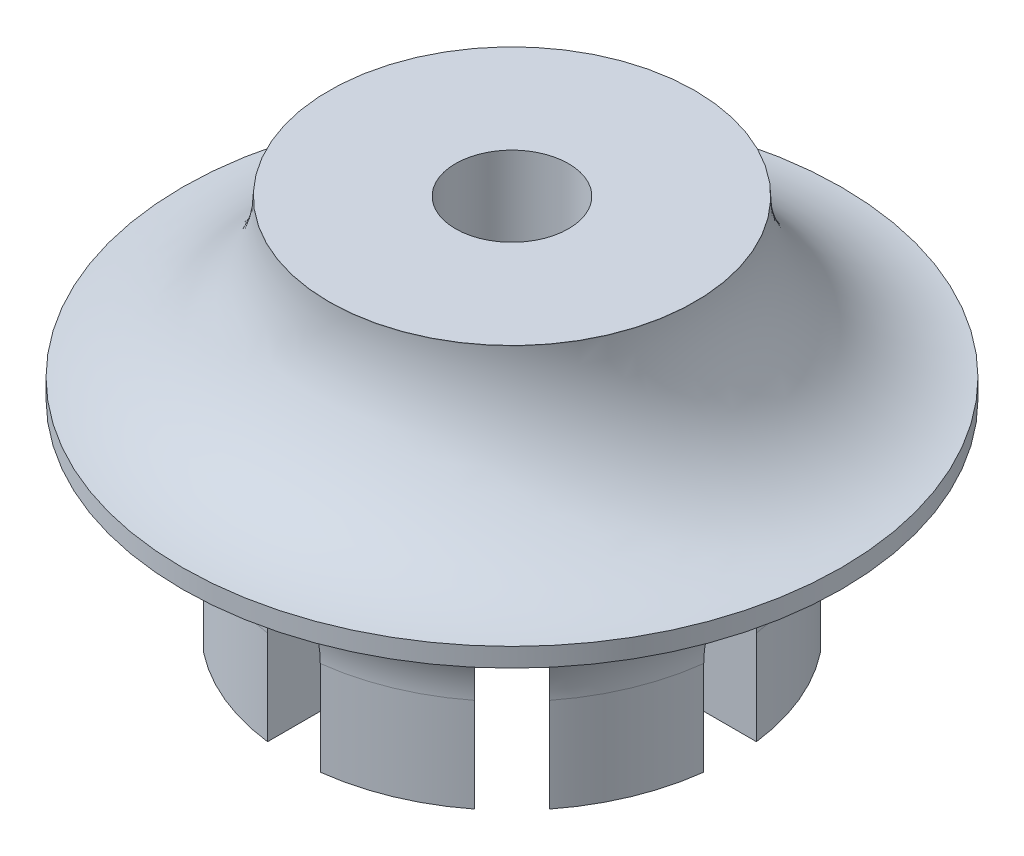
SolidWorks part; units mm, degrees
ref_plane "Front Plane" through (0, 0, 0) normal (0, 0, 1) x (1, 0, 0)
ref_plane "Top Plane" through (0, 0, 0) normal (0, 1, 0) x (1, 0, 0)
ref_plane "Right Plane" through (0, 0, 0) normal (1, 0, 0) x (0, 0, -1)
sketch "Sketch1" plane through (0, 0, 0) normal (0, 1, 0) x (1, 0, 0)
  circle A0 centre (0, 0) radius 7.4041
extrude "Boss-Extrude1" add sketch "Sketch1" along normal blind 6.35
sketch "Sketch2" plane through (0, 0, 0) normal (0, -1, 0) x (1, 0, 0)
  circle A0 centre (0, 0) radius 13.335
extrude "Boss-Extrude2" add sketch "Sketch2" along normal blind 0.762
sketch "Sketch3" plane through (0, -0.762, 0) normal (0, -1, 0) x (1, 0, 0)
  circle A0 centre (0, 0) radius 8.89
  dimension "D1" = 17.78
extrude "Boss-Extrude3" add sketch "Sketch3" along normal blind 8.128
fillet "Fillet1" radius 4.318 1 edges at (0, -0.762, -8.89)
fillet "Fillet2" radius 6.35 1 edges at (0, 0, -7.4041)
sketch "Sketch4" plane through (0, -8.89, 0) normal (0, -1, 0) x (1, 0, 0)
  circle A0 centre (0, 0) radius 4.826
  dimension "D1" = 9.652
extrude "Cut-Extrude1" cut sketch "Sketch4" against normal blind 8.128
sketch "Sketch5" plane through (0, -8.89, 0) normal (0, -1, 0) x (1, 0, 0)
  line L0 (-1.0668, -10.9423) -> (1.0668, -10.9423)
  line L1 (-1.0668, 0) -> (-1.0668, -10.9423)
  line L2 (1.0668, 0) -> (1.0668, -10.9423)
  line L3 (-1.0668, 0) -> (1.0668, 0)
  dimension "D1" = 1.0668
  dimension "D2" = 1.0668
extrude "Cut-Extrude2" cut sketch "Sketch5" against normal blind 7.366
pattern_circular "CirPattern2" count 8 over 360 about axis through (0, -0.762, 0) along (0, -1, 0) of "Cut-Extrude2" reverse direction yes
sketch "Sketch8" plane through (0, -1.524, 0) normal (0, -1, 0) x (1, 0, 0)
  circle A0 centre (0, 0) radius 4.826
  circle A1 centre (0, 0) radius 2.286
  dimension "D1" = 9.652
  dimension "D2" = 4.572
extrude "Boss-Extrude4" add sketch "Sketch8" against normal blind 1.27
sketch "Sketch10" plane through (0, 6.35, 0) normal (0, 1, 0) x (1, 0, 0)
  line L0 (2.2825, 0.1272) -> (-0.1272, -2.2825)
  circle A0 centre (0, 0) radius 2.286
  dimension "D1" = 4.572
  dimension "D2" = 1.524
extrude "Cut-Extrude5" cut sketch "Sketch10" against normal through all contours L0 A0 region at (-0.1595, 6.35, -0.1595)
sketch "Sketch11" plane through (0, 6.35, 0) normal (0, 1, 0) x (1, 0, 0)
  circle A0 centre (0, 0) radius 2.286
extrude "Cut-Extrude6" cut sketch "Sketch11" against normal blind 2.032
